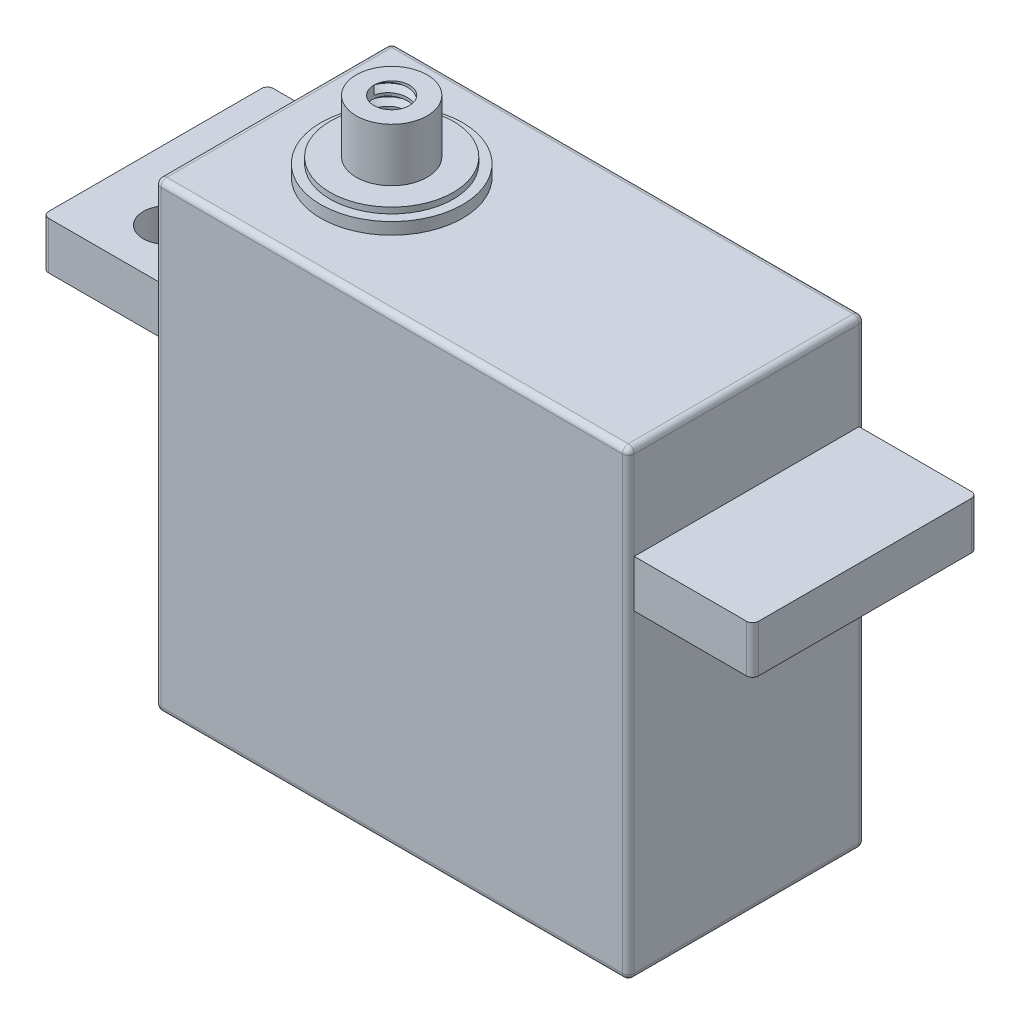
SolidWorks part; units mm, degrees
ref_plane "前视基准面" through (0, 0, 0) normal (0, 0, 1) x (1, 0, 0)
ref_plane "上视基准面" through (0, 0, 0) normal (0, 1, 0) x (1, 0, 0)
ref_plane "右视基准面" through (0, 0, 0) normal (1, 0, 0) x (0, 0, -1)
sketch "草图1" plane through (0, 0, 0) normal (0, 0, 1) x (1, 0, 0)
  line L1 (0, 0) -> (40, 0)
  line L2 (0, 0) -> (0, -39)
  line L3 (0, -39) -> (40, -39)
  line L4 (40, 0) -> (40, -39)
  dimension "D1" = 39
  dimension "D2" = 40
extrude "凸台-拉伸1" add sketch "草图1" along normal blind 20
ref_plane "基准面4" through (0, 0, 0) normal (-1, 0, 0) x (0, 0, 1)
sketch "草图2" plane through (0, 0, 0) normal (-1, 0, 0) x (0, 0, 1)
  line L3 (0.5, -12) -> (19.5, -12)
  line L7 (0.5, -12) -> (0.5, -8)
  line L8 (0.5, -8) -> (19.5, -8)
  line L9 (19.5, -8) -> (19.5, -12)
  line L10 (0, 0) -> (0, -39) construction
  line L11 (20, 0) -> (20, -39) construction
  line L12 (20, 0) -> (0, 0) construction
  dimension "D1" = 0.5
  dimension "D2" = 0.5
  dimension "D3" = 4
  dimension "D4" = 8
extrude "凸台-拉伸2" add sketch "草图2" along normal blind 10
ref_plane "基准面5" through (40, 0, 0) normal (1, 0, 0) x (0, 0, -1)
sketch "草图3" plane through (40, 0, 0) normal (1, 0, 0) x (0, 0, -1)
  line L3 (-19.5, -12) -> (-0.5, -12)
  line L6 (-19.5, -12) -> (-19.5, -8)
  line L7 (-19.5, -8) -> (-0.5, -8)
  line L8 (-0.5, -8) -> (-0.5, -12)
  line L9 (0, -39) -> (0, 0) construction
  line L10 (-20, -39) -> (-20, 0) construction
  line L11 (-20, 0) -> (0, 0) construction
  dimension "D1" = 0.5
  dimension "D2" = 0.5
  dimension "D3" = 4
  dimension "D4" = 8
extrude "凸台-拉伸3" add sketch "草图3" along normal blind 10
ref_plane "基准面6" through (0, 0, 0.5) normal (0, 0, -1) x (1, 0, 0)
ref_plane "基准面7" through (0, 0, 19.5) normal (0, 0, 1) x (1, 0, 0)
ref_plane "基准面8" through (0, 0, 0) normal (0, 1, 0) x (1, 0, 0)
sketch "草图6" plane through (0, 0, 0) normal (0, 1, 0) x (1, 0, 0)
  line L0 (-10, -10) -> (40, -10) construction
  line L3 (0, 4.125) -> (0, -4.125) construction
  line L4 (-10, -19.5) -> (-10, -0.5) construction
  line L5 (40, -20) -> (40, 0) construction
  circle A0 centre (10, -10) radius 6
  dimension "D1" = 12
  dimension "D2" = 10
extrude "凸台-拉伸4" add sketch "草图6" along normal blind 1
ref_plane "基准面9" through (0, 1, 0) normal (0, 1, 0) x (1, 0, 0)
sketch "草图7" plane through (0, 1, 0) normal (0, 1, 0) x (1, 0, 0)
  circle A0 centre (10, -10) radius 5.2082
extrude "凸台-拉伸5" add sketch "草图7" along normal blind 0.5
ref_plane "基准面10" through (0, 1.5, 0) normal (0, 1, 0) x (1, 0, 0)
sketch "草图8" plane through (0, 1.5, 0) normal (0, 1, 0) x (1, 0, 0)
  circle A0 centre (10, -10) radius 3
  dimension "D1" = 6
extrude "凸台-拉伸6" add sketch "草图8" along normal blind 4.5
ref_plane "基准面11" through (0, 6, 0) normal (0, 1, 0) x (1, 0, 0)
sketch "草图9" plane through (0, 6, 0) normal (0, 1, 0) x (1, 0, 0)
  circle A0 centre (10, -10) radius 1.5
  dimension "D1" = 3
extrude "切除-拉伸3" cut sketch "草图9" against normal blind 4.5
thread "螺纹线1" pitch 1 start angle 0, offset 0, length 0, pitch 1, diameter 3
ref_plane "基准面12" through (8.5, 6, 10) normal (0, 0, 1) x (-1, 0, 0)
sketch "螺纹线轮廓1" plane through (8.5, 6, 10) normal (0, 0, 1) x (-1, 0, 0)
  line L0 (0, 0) -> (0, 1) construction
  line L1 (0, 0) -> (0.5413, 0.3125)
  line L2 (0.5413, 0.3125) -> (0.5413, 0.4375)
  line L3 (0.5413, 0.4375) -> (0, 0.75)
  line L4 (0.5413, 0.375) -> (0, 0.375) construction
  line L11 (0, 0) -> (0, 0.75)
  point P2 (0, 0)
  dimension "Pitch" = 1
  dimension "Profile_Angle" = 60
  dimension "Profile_Land" = 0.125
  dimension "Profile_Height" = 0.5413
fillet "圆角1" radius 0.5 1 edges at (20, 0, 20)
fillet "圆角2" radius 0.5 1 edges at (20, 0, 0)
fillet "圆角7" radius 0.5 5 edges at (0, -19.75, 20) (0, -0.1464, 19.8536) (0, -19.75, 0) (0, -0.1464, 0.1464) (0, 0, 10)
fillet "圆角8" radius 0.5 5 edges at (40, -19.75, 20) (40, -0.1464, 19.8536) (40, -19.75, 0) (40, -0.1464, 0.1464) (40, 0, 10)
fillet "圆角15" radius 0.5 8 edges at (20, -39, 0) (0.1464, -39, 0.1464) (0, -39, 10) (0.1464, -39, 19.8536) (20, -39, 20) (40, -39, 10) (39.8536, -39, 19.8536) (39.8536, -39, 0.1464)
ref_plane "基准面13" through (0, -8, 0) normal (0, 1, 0) x (1, 0, 0)
sketch "草图16" plane through (0, -8, 0) normal (0, 1, 0) x (1, 0, 0)
  line L0 (-10, -10) -> (0, -10) construction
  line L1 (-10, -19.5) -> (-10, -0.5) construction
  line L2 (0, -19.5) -> (0, -0.5) construction
  circle A0 centre (-4, -5) radius 2
  circle A1 centre (-4, -15) radius 2
  dimension "D1" = 4
  dimension "D2" = 4
  dimension "D3" = 10
extrude "切除-拉伸4" cut sketch "草图16" against normal blind 4.5
fillet "圆角16" radius 0.5 1 edges at (-10, -10, 19.5)
fillet "圆角17" radius 0.5 1 edges at (-10, -10, 0.5)
fillet "圆角18" radius 0.5 1 edges at (50, -10, 19.5)
fillet "圆角19" radius 0.5 1 edges at (50, -10, 0.5)
